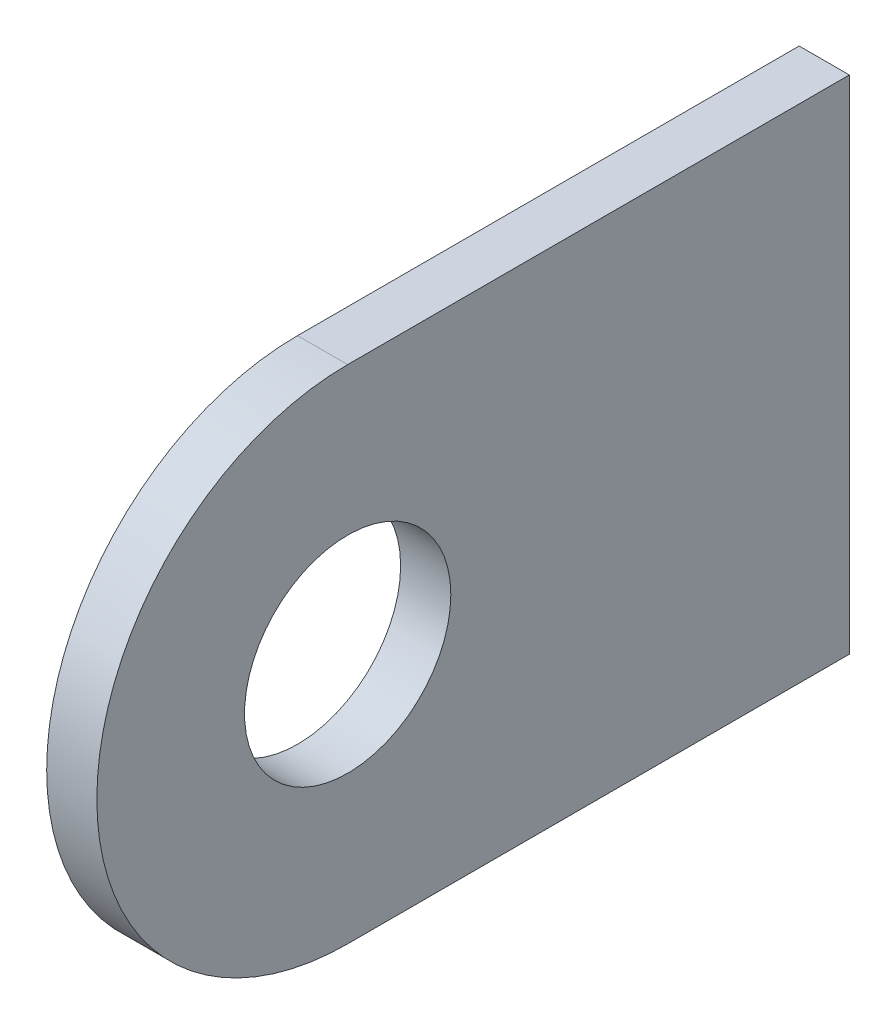
SolidWorks part; units mm, degrees
material "AISI 4130 Steel, annealed at 865C"
ref_plane "X-Y Datum" through (0, 0, 0) normal (0, 0, 1) x (1, 0, 0)
ref_plane "X-Z Datum" through (0, 0, 0) normal (0, 1, 0) x (1, 0, 0)
ref_plane "Y-Z Datum" through (0, 0, 0) normal (1, 0, 0) x (0, 0, -1)
sketch "Sketch1" plane through (0, 0, 0) normal (1, 0, 0) x (0, 0, -1)
  line L0 (0, -7.9375) -> (0, 7.9375)
  line L4 (-15.875, -7.9375) -> (0, -7.9375)
  line L5 (-15.875, 7.9375) -> (0, 7.9375)
  arc A1 (-15.875, -7.9375) -> (-15.875, 7.9375) centre (-15.875, 0) cw
  point P4 (0, 0)
  dimension "D1" = 15.875
  dimension "D2" = 7.9375
extrude "Boss-Extrude1" add sketch "Sketch1" along normal blind 1.5875
hole_wizard "1/4 Clearance Hole1" positions "Sketch2" profile "Sketch3" hole size "1/4" standard "ANSI Inch" end condition through all
sketch "Sketch2" plane through (1.5875, 0, 0) normal (1, 0, 0) x (0, 0, -1)
  point P0 (-15.875, 0)
sketch "Sketch3" plane through (1.5875, 0, 15.875) normal (0, 1, 0) x (0, 0, -1)
  line L0 (0, 0) -> (0, 1.5875)
  line L1 (0, 1.5875) -> (3.2639, 1.5875)
  line L2 (3.2639, 1.5875) -> (3.2639, 0)
  line L5 (3.2639, 0) -> (0, 0)
  line L11 (0, -6.35) -> (0, 107.95) construction
  dimension "Thru Hole Dia." = 6.5278
  dimension "Thru Hole Depth" = 1.5875
